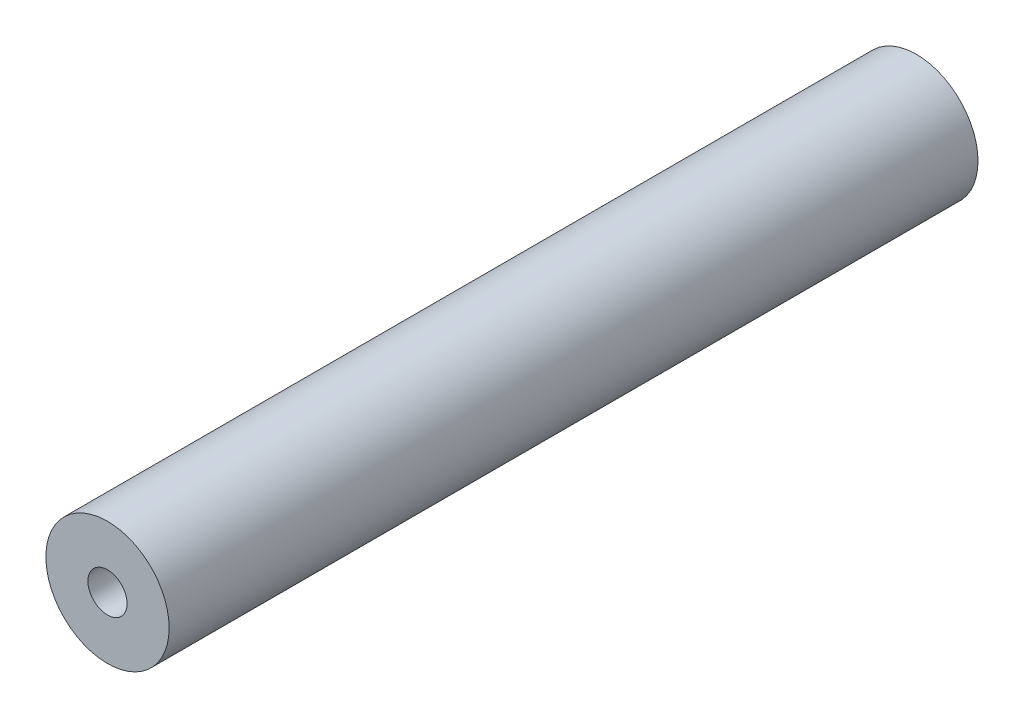
SolidWorks part; units mm, degrees
material "6061-T6 (SS)"
ref_plane "Front Plane" through (0, 0, 0) normal (0, 0, 1) x (1, 0, 0)
ref_plane "Top Plane" through (0, 0, 0) normal (0, 1, 0) x (1, 0, 0)
ref_plane "Right Plane" through (0, 0, 0) normal (1, 0, 0) x (0, 0, -1)
sketch "Sketch1" plane through (0, 0, 0) normal (0, 0, 1) x (1, 0, 0)
  circle A1 centre (0, 0) radius 6.35
  dimension "D2" = 12.7
extrude "Boss-Extrude1" add sketch "Sketch1" along normal mid plane 83.345 contours A1 region at (0, 0, 0)
hole_wizard "#10-32 Tapped Hole1" positions "3DSketch1" profile "Sketch2" tap size "#10-32" standard "ANSI Inch"
sketch3d "3DSketch1"
  line L0 (0, 0, 41.6725) -> (0, 0, -41.6725) construction
  point P0 (0, 0, -41.6725)
  point P4 (0, 0, 41.6725)
sketch "Sketch2" plane through (0, 0, -41.6725) normal (1, 0, 0) x (0, 1, 0)
  line L0 (0, 0) -> (0, 13.2428)
  line L1 (0, 13.2428) -> (2.0193, 12.0294)
  line L2 (2.0193, 12.0294) -> (2.0193, 0)
  line L5 (2.0193, 0) -> (0, 0)
  line L10 (0, 13.2428) -> (-2.0193, 12.0294) construction
  line L11 (0, -6.35) -> (0, 107.95) construction
  dimension "Tap Drill Dia." = 4.0386
  dimension "Tap Drill Depth" = 12.0294
  dimension "Drill Angle" = 118
cosmetic thread "Hole Thread1"
cosmetic thread "Hole Thread2"
